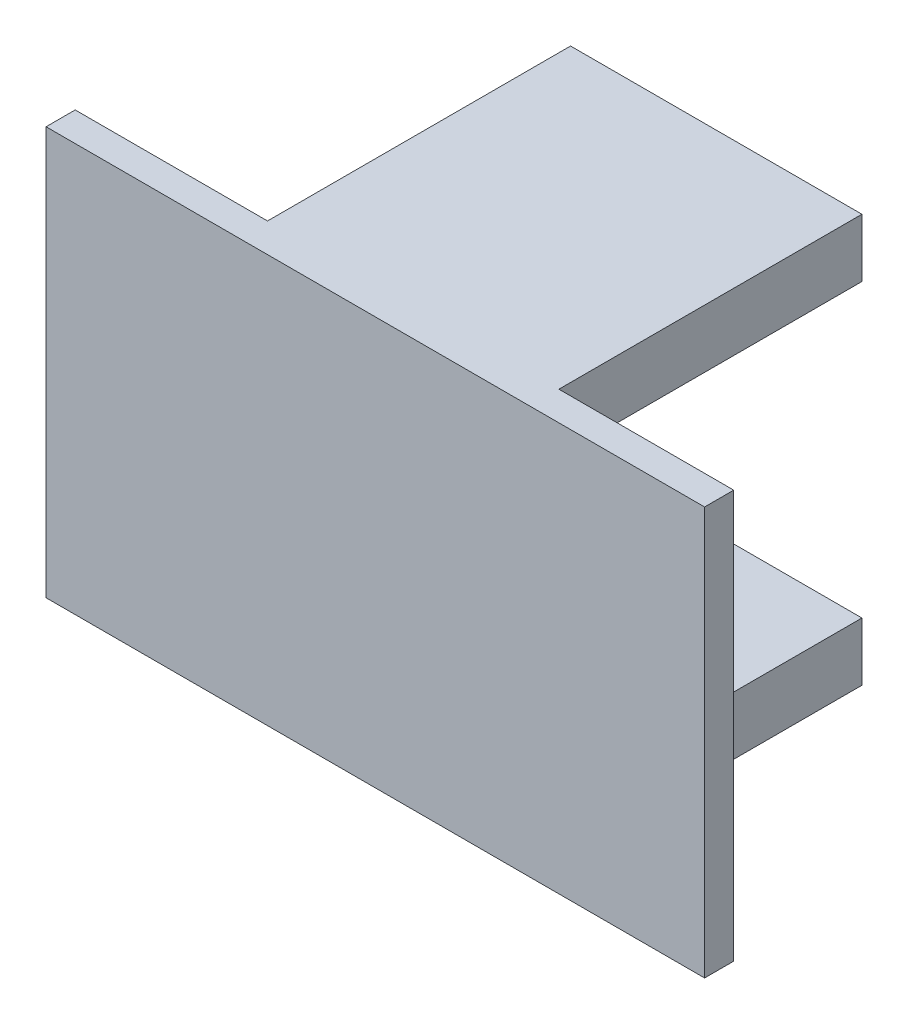
SolidWorks part; units mm, degrees
ref_plane "前视基准面" through (0, 0, 0) normal (0, 0, 1) x (1, 0, 0)
ref_plane "上视基准面" through (0, 0, 0) normal (0, 1, 0) x (1, 0, 0)
ref_plane "右视基准面" through (0, 0, 0) normal (1, 0, 0) x (0, 0, -1)
sketch "草图1" plane through (0, 0, 0) normal (0, 0, 1) x (1, 0, 0)
  line L1 (-56.5, 35) -> (56.5, 35)
  line L2 (-56.5, 35) -> (-56.5, -35)
  line L3 (-56.5, -35) -> (56.5, -35)
  line L4 (56.5, 35) -> (56.5, -35)
  line L5 (-56.5, 35) -> (56.5, -35) construction
  line L6 (-56.5, -35) -> (56.5, 35) construction
  point P0 (0, 0)
  dimension "D1" = 113
  dimension "D2" = 70
extrude "凸台-拉伸1" add sketch "草图1" along normal blind 5 contours L1 L4 L3 L2
sketch "草图2" plane through (0, 0, 0) normal (0, 0, -1) x (-1, 0, 0)
  line L0 (56.5, -35) -> (-56.5, -35) construction
  line L1 (-56.5, 35) -> (-56.5, -35) construction
  line L2 (56.5, 35) -> (-56.5, 35) construction
  line L3 (-26.5, -35) -> (23.5, -35)
  line L4 (-26.5, -35) -> (-26.5, -25)
  line L5 (-26.5, -25) -> (23.5, -25)
  line L6 (23.5, -35) -> (23.5, -25)
  line L7 (-26.5, 35) -> (23.5, 35)
  line L8 (-26.5, 35) -> (-26.5, 25)
  line L9 (-26.5, 25) -> (23.5, 25)
  line L10 (23.5, 35) -> (23.5, 25)
  point P0 (-26.5, -35)
  dimension "D1" = 30
  dimension "D2" = 50
  dimension "D3" = 10
  dimension "D4" = 30
  dimension "D5" = 50
  dimension "D6" = 10
extrude "凸台-拉伸2" add sketch "草图2" along normal blind 52
sketch "草图3" plane through (0, 0, 0) normal (0, 0, -1) x (-1, 0, 0)
  line L0 (-26.5, 35) -> (-56.5, 35) construction
  line L2 (-56.5, 35) -> (-56.5, -35) construction
  line L3 (56.5, 35) -> (23.5, 35) construction
  line L4 (56.5, 35) -> (56.5, -35) construction
  circle A0 centre (-34.5, 10) radius 4
  circle A1 centre (34.5, 10) radius 4
  point P0 (-34.5, 10)
  point P9 (40, 35)
  dimension "D3" = 25
  dimension "D1" = 25
  dimension "D2" = 22
  dimension "D4" = 22
